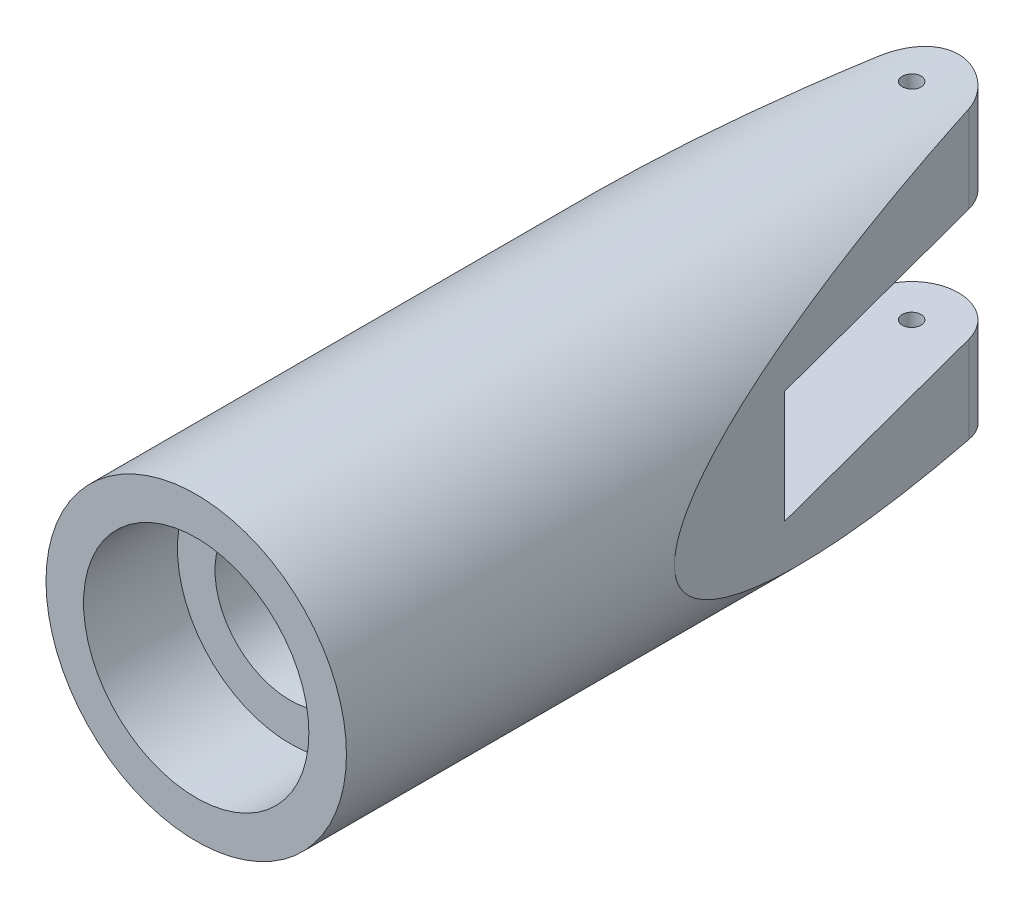
SolidWorks part; units mm, degrees
ref_plane "Front" through (0, 0, 0) normal (0, 0, 1) x (1, 0, 0)
ref_plane "Top" through (0, 0, 0) normal (0, 1, 0) x (1, 0, 0)
ref_plane "Right" through (0, 0, 0) normal (1, 0, 0) x (0, 0, -1)
sketch "Sketch2" plane through (0, 0, 0) normal (1, 0, 0) x (0, 0, -1)
  line L0 (-12.9752, 0) -> (14.864, 0) construction
  line L1 (-20.4, 4) -> (0, 4)
  line L2 (0, 4) -> (0, 3)
  line L3 (0, 3) -> (20, 3)
  line L4 (20, 3) -> (20, 8)
  line L5 (20, 8) -> (-25.4, 8)
  line L6 (-25.4, 8) -> (-25.4, 6)
  line L7 (-25.4, 6) -> (-20.4, 6)
  line L8 (-20.4, 6) -> (-20.4, 4)
  dimension "D1" = 4
  dimension "D2" = 3
  dimension "D3" = 20
  dimension "D4" = 25.4
  dimension "D5" = 8
  dimension "D6" = 2
  dimension "D7" = 5
revolve "Revolve1" add sketch "Sketch2" angle 360 about L0
sketch "Sketch3" plane through (0, 0, 0) normal (0, 1, 0) x (1, 0, 0)
  line L0 (11.6903, 25) -> (-11.6903, 25)
  line L1 (17.3799, -21.9904) -> (-18.1253, -21.9904) construction
  line L2 (-2.4181, 13.3347) -> (-11.6903, -21.9904)
  line L3 (2.4181, 13.3347) -> (11.6903, -21.9904)
  line L4 (-11.6903, 25) -> (-11.6903, -21.9904)
  line L5 (11.6903, 25) -> (11.6903, -21.9904)
  line L6 (-8, -14.3434) -> (-8, 9.482) construction
  line L7 (-8, 20) -> (-8, -25.4) construction
  line L8 (8, 9.482) -> (8, -15.7471) construction
  line L9 (0, 34.4612) -> (0, -14.3434) construction
  arc A0 (2.4181, 13.3347) -> (-2.4181, 13.3347) centre (0, 12.7) ccw
  circle A1 centre (0, 12.7) radius 0.5
  point P0 (17.3799, 3.8717)
  point P1 (0, 25)
  dimension "D2" = 1
  dimension "D4" = 2.5
  dimension "D5" = 12.7
  dimension "D1" = 25
  dimension "D3" = 16
extrude "Cut-Extrude2" cut sketch "Sketch3" against normal through all both and the other way through all contours A0 L3 L5 L0 L4 L2 | L0 L4 L2 A0 L3 L5 region at (11.1654, 0, -1.5048)
sketch "Sketch4" plane through (0, 0, 0) normal (1, 0, 0) x (0, 0, -1)
  line L0 (12.5056, 0) -> (0, 0) construction
  line L1 (25.0111, -3) -> (0, -3)
  line L2 (25.0111, -3) -> (25.0111, 3)
  line L3 (25.0111, 3) -> (0, 3)
  line L4 (0, -3) -> (0, 3)
  line L5 (25.0111, -3) -> (0, 3) construction
  line L6 (25.0111, 3) -> (0, -3) construction
  point P0 (12.5056, 0)
  point P8 (0, 0)
  dimension "D1" = 0
  dimension "D2" = 6
extrude "Cut-Extrude3" cut sketch "Sketch4" against normal through all both and the other way through all
extrude "Cut-Extrude4" cut sketch "Sketch3<4>" along normal through all and the other way blind 6 contours A1
sketch "Sketch3<4>" plane through (0, 0, 0) normal (0, 1, 0) x (1, 0, 0) same geometry as "Sketch3"
